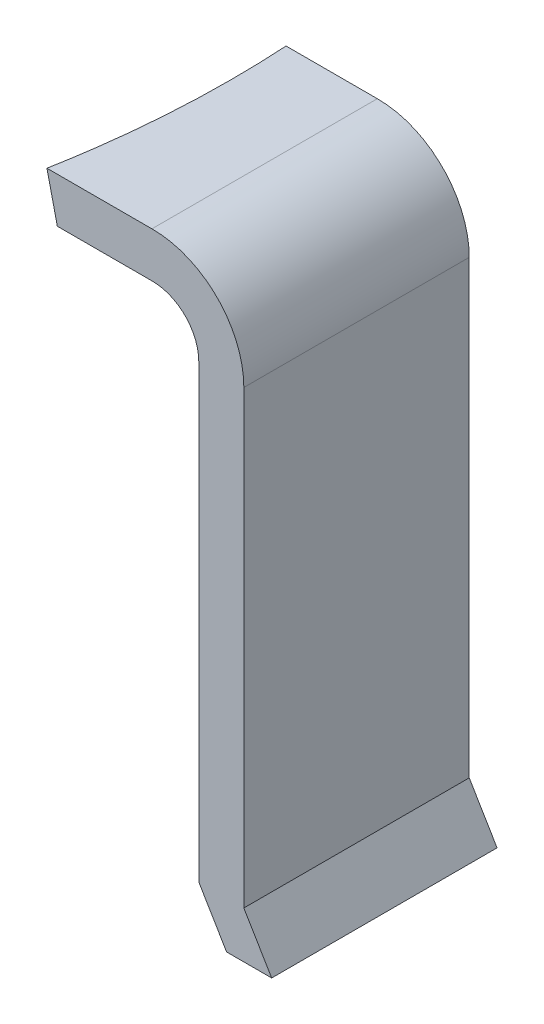
SolidWorks part; units mm, degrees
ref_plane "Front Plane" through (0, 0, 0) normal (0, 0, 1) x (1, 0, 0)
ref_plane "Top Plane" through (0, 0, 0) normal (0, 1, 0) x (1, 0, 0)
ref_plane "Right Plane" through (0, 0, 0) normal (1, 0, 0) x (0, 0, -1)
sketch "Sketch1" plane through (0, 0, 0) normal (0, 0, 1) x (1, 0, 0)
  line L1 (-0.2753, 0.6183) -> (-0.2753, 20.6183)
  line L3 (-4.3535, 22.6748) -> (-4.3535, 24.6748)
  line L4 (-2.2753, 20.6183) -> (-2.2753, 0.6183)
  line L10 (-0.2753, 0.6183) -> (0.9594, -1.4542)
  line L11 (0.9594, -1.4542) -> (-1.0406, -1.4542)
  line L12 (-1.0406, -1.4542) -> (-2.2753, 0.6183)
  arc A1 (-0.2753, 20.6183) -> (-4.3535, 24.6748) centre (-4.3318, 20.6183) ccw
  arc A3 (-2.2753, 20.6183) -> (-4.3535, 22.6748) centre (-4.3318, 20.6183) ccw
  dimension "D2" = 2
  dimension "D1" = 20
  dimension "D3" = 2
  dimension "D5" = 2
extrude "Boss-Extrude1" add sketch "Sketch1" along normal blind 10
sketch "Sketch2" plane through (-4.3535, 0, 0) normal (-1, 0, 0) x (0, 0, 1)
  line L1 (0, 24.6748) -> (10, 24.6748)
  line L2 (0, 24.6748) -> (0, 22.6748)
  line L3 (0, 22.6748) -> (10, 22.6748)
  line L4 (10, 24.6748) -> (10, 22.6748)
extrude "Boss-Extrude2" add sketch "Sketch2" along normal blind 5
sketch "Sketch7" plane through (0, 0, 10) normal (0, 0, 1) x (1, 0, 0)
  line L0 (-9.3535, 24.6748) -> (-8.8917, 22.6748)
  line L1 (-9.3535, 22.6748) -> (-4.3535, 22.6748) construction
  line L2 (-9.3535, 22.6748) -> (-9.3535, 24.6748)
  arc A0 (-8.8917, 22.6748) -> (-9.3535, 22.6748) centre (-9.1226, 23.6748) cw
  dimension "D1" = 13
extrude "Cut-Extrude3" cut sketch "Sketch7" against normal through all
sketch "Sketch8" plane through (0, 0, 10) normal (0, 0, 1) x (1, 0, 0)
  line L5 (-9.1226, 23.6748) -> (-50.5333, 14.1144)
  line L6 (-8.8917, 22.6748) -> (-9.3535, 24.6748) construction
  line L7 (-50.5333, 14.1144) -> (-50.5558, 14.2118)
  line L8 (-50.5558, 14.2118) -> (-9.1451, 23.7722)
  line L9 (-9.1451, 23.7722) -> (-9.1226, 23.6748)
  dimension "D1" = 0.1
  dimension "D2" = 42.5
  dimension "D3" = 90
extrude "Boss-Extrude7" add sketch "Sketch8" against normal through all
sketch "Sketch10" plane through (-5.6733, 24.5738, 0) normal (-0.225, 0.9744, 0) x (0.9744, 0.225, 0)
  line L0 (-3.5631, 0) -> (-3.5631, -10) construction
  circle A0 centre (-45.0631, -2.5) radius 42.5
  dimension "D1" = 41.5
  dimension "D2" = 85
extrude "Cut-Extrude5" cut sketch "Sketch10" against normal blind 2 and the other way blind 2
